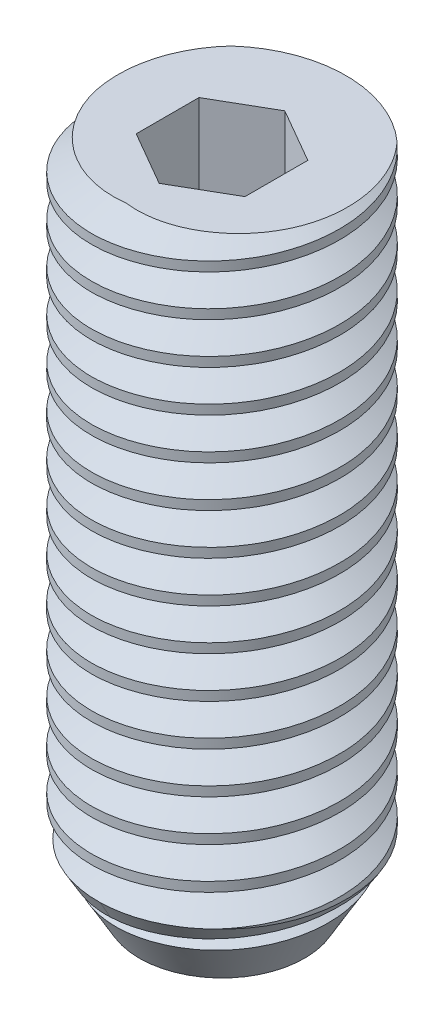
SolidWorks part; units mm, degrees
ref_plane "Front Plane" through (0, 0, 0) normal (0, 0, 1) x (1, 0, 0)
ref_plane "Top Plane" through (0, 0, 0) normal (0, 1, 0) x (1, 0, 0)
ref_plane "Right Plane" through (0, 0, 0) normal (1, 0, 0) x (0, 0, -1)
sketch "Sketch1" plane through (0, 0, 0) normal (0, 1, 0) x (1, 0, 0)
  circle A0 centre (0, 0) radius 1.5
  dimension "D1" = 3
extrude "Boss-Extrude1" add sketch "Sketch1" along normal blind 8 contours A0
sketch "Sketch2" plane through (0, 8, 0) normal (0, 1, 0) x (1, 0, 0)
  line L1 (0, 0.76) -> (-0.6582, 0.38)
  line L2 (-0.6582, 0.38) -> (-0.6582, -0.38)
  line L3 (-0.6582, -0.38) -> (0, -0.76)
  line L4 (0, -0.76) -> (0.6582, -0.38)
  line L5 (0.6582, -0.38) -> (0.6582, 0.38)
  line L6 (0.6582, 0.38) -> (0, 0.76)
  circle A1 centre (0, 0) radius 0.6582 construction
  dimension "D2" = 1.52
extrude "Cut-Extrude1" cut sketch "Sketch2" against normal blind 1.2 contours L1 L2 L3 L4 L5 L6
chamfer "Chamfer1" distance 0.5 angle 60 1 edges at (0, 0, 1.5)
sketch "Sketch14" plane through (0, 8, 0) normal (0, 1, 0) x (1, 0, 0)
  circle A1 centre (0, 0) radius 1.5
  circle A2 centre (0, 0) radius 1.5
  dimension "D1" = 0
curve "Helix/Spiral2" pitch 0.5 height 8.375 turns 16.75
sketch "Sketch15" plane through (0, 0, 0) normal (1, 0, 0) x (0, 0, -1)
  line L1 (-1.1667, 8) -> (-1.6667, 8.2887)
  line L2 (-1.6667, 8.2887) -> (-1.6667, 7.7113)
  line L3 (-1.6667, 7.7113) -> (-1.1667, 8)
  circle A0 centre (-1.5, 8) radius 0.1667 construction
  dimension "D1" = 0.5
sweep "Cut-Sweep13" cut profiles "Sketch15" path "Helix/Spiral2"
